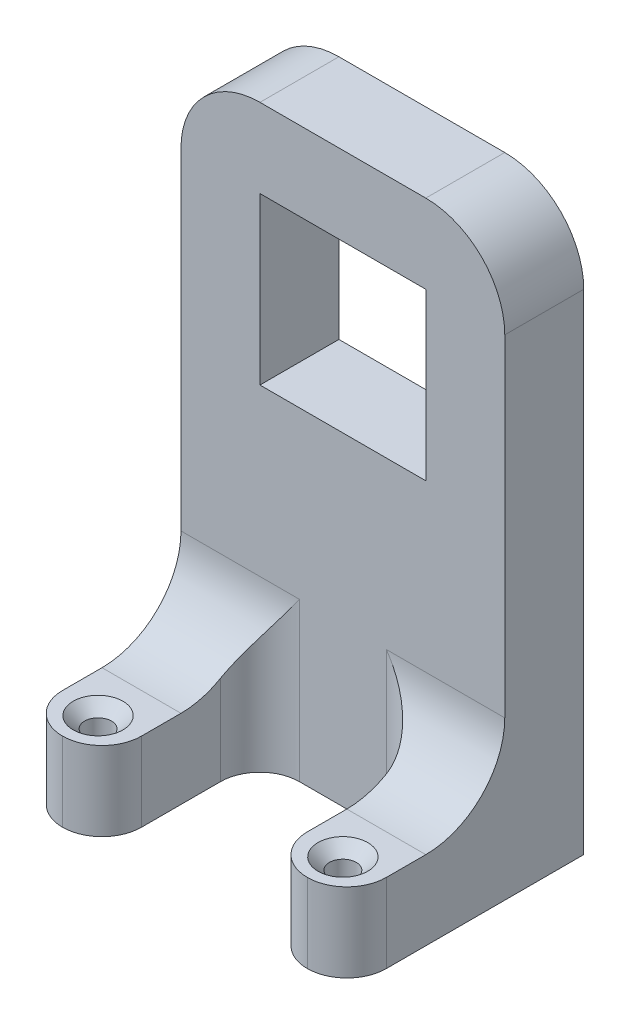
SolidWorks part; units mm, degrees
ref_plane "Plan de face" through (0, 0, 0) normal (0, 0, 1) x (1, 0, 0)
ref_plane "Plan de dessus" through (0, 0, 0) normal (0, 1, 0) x (1, 0, 0)
ref_plane "Plan de droite" through (0, 0, 0) normal (1, 0, 0) x (0, 0, -1)
sketch "Esquisse1" plane through (0, 0, 0) normal (0, 0, 1) x (1, 0, 0)
  line L0 (0, 0) -> (41, 0)
  line L1 (0, 0) -> (41, 0) construction
  line L2 (0, 0) -> (0, 72) construction
  line L3 (0, 72) -> (41, 72) construction
  line L4 (41, 0) -> (41, 72) construction
  line L5 (41, 0) -> (41, 72)
  line L6 (41, 72) -> (0, 72)
  line L7 (0, 72) -> (0, 0)
  line L9 (10, 62) -> (31, 62)
  line L10 (10, 62) -> (10, 41)
  line L11 (10, 41) -> (31, 41)
  line L12 (31, 62) -> (31, 41)
  dimension "D1" = 41
  dimension "D2" = 72
  dimension "D3" = 10
  dimension "D4" = 10
  dimension "D5" = 10
  dimension "D6" = 41
extrude "Boss.-Extru.1" add sketch "Esquisse1" along normal blind 10
sketch "Esquisse3" plane through (0, 0, 10) normal (0, 0, 1) x (1, 0, 0)
  line L0 (31, 0) -> (41, 0)
  line L3 (0, 10) -> (10, 10)
  line L4 (0, 72) -> (0, 0)
  line L5 (0, 0) -> (41, 0)
  line L6 (41, 0) -> (41, 72)
  line L7 (41, 72) -> (0, 72)
  line L8 (0, 10) -> (0, 0)
  line L9 (0, 0) -> (10, 0)
  line L12 (10, 0) -> (10, 10)
  line L14 (41, 0) -> (41, 10)
  line L15 (41, 10) -> (31, 10)
  line L16 (31, 0) -> (31, 10)
  line L17 (0, 0) -> (41, 0) construction
  dimension "D2" = 10
  dimension "D3" = 10
  dimension "D4" = 10
  dimension "D5" = 10
  dimension "D1" = 0
extrude "Boss.-Extru.2" add sketch "Esquisse3" along normal blind 20
sketch "Esquisse4" plane through (0, 10, 0) normal (0, 1, 0) x (1, 0, 0)
  line L0 (0, -30) -> (0, -10) construction
  line L2 (41, -30) -> (41, -10) construction
  line L4 (41, -30) -> (31, -30) construction
  line L5 (10, -30) -> (0, -30) construction
  circle A0 centre (5, -25.5) radius 1.5
  circle A1 centre (36, -25.5) radius 1.5
  dimension "D3" = 3
  dimension "D4" = 3
  dimension "D1" = 5
  dimension "D5" = 5
  dimension "D2" = 4.5
  dimension "D6" = 4.5
hole_wizard "Fraisage pour vis à tête fraisée M31" positions "Esquisse5" profile "Esquisse6" countersink size "M3" standard "ISO" end condition through all
sketch "Esquisse5" plane through (0, 10, 0) normal (0, 1, 0) x (1, 0, 0)
  point P0 (5, -25.5)
  point P3 (36, -25.5)
sketch "Esquisse6" plane through (5, 10, 25.5) normal (1, 0, 0) x (0, 0, 1)
  line L0 (0, 0) -> (0, 10)
  line L1 (0, 10) -> (1.7, 10)
  line L2 (1.7, 10) -> (1.7, 1.45)
  line L3 (1.7, 1.45) -> (3.15, 0)
  line L5 (3.15, 0) -> (0, 0)
  line L6 (-1.7, 1.45) -> (-3.15, 0) construction
  line L11 (0, -6.35) -> (0, 107.95) construction
  dimension "Diamètre du perçage jusqu'au prochain" = 3.4
  dimension "Profondeur du perçage jusqu'au prochain" = 10
  dimension "Diamètre du fraisage entrant" = 6.3
  dimension "Angle du fraisage entrant" = 90
ref_plane "Plan1" through (0, 0, 5) normal (0, 0, 1) x (1, 0, 0)
fillet "Congé2" radius 10 2 edges at (0, 72, 5) (41, 72, 5)
fillet "Congé3" radius 5 6 edges at (10, 5, 10) (31, 5, 10) (41, 5, 30) (31, 5, 30) (10, 5, 30) (0, 5, 30)
fillet "Congé4" radius 10 2 edges at (33.5, 10, 10) (7.5, 10, 10)
equation "\"largeur_cremail\"= 21"
equation "\"hauteur_cremail\"= 21"
equation "\"epaiss_cadre\"= 10"
equation "\"hauteur_basecremail_sol\"= 122 - 76 - 15"
equation "\"D1@Esquisse1\"=\"largeur_cremail\"+\"epaiss_cadre\"*2"
equation "\"D2@Esquisse1\"=\"hauteur_basecremail_sol\"+\"hauteur_cremail\"+\"epaiss_cadre\"*2"
equation "\"D3@Esquisse1\"=\"epaiss_cadre\""
equation "\"D4@Esquisse1\"=\"epaiss_cadre\""
equation "\"D5@Esquisse1\"=\"epaiss_cadre\""
equation "\"D6@Esquisse1\"=\"hauteur_basecremail_sol\"+\"epaiss_cadre\""
equation "\"D1@Boss.-Extru.1\"=\"epaiss_cadre\""
equation "\"D1@Esquisse4\"=\"epaiss_cadre\"/2"
equation "\"D5@Esquisse4\"=\"epaiss_cadre\"/2"
